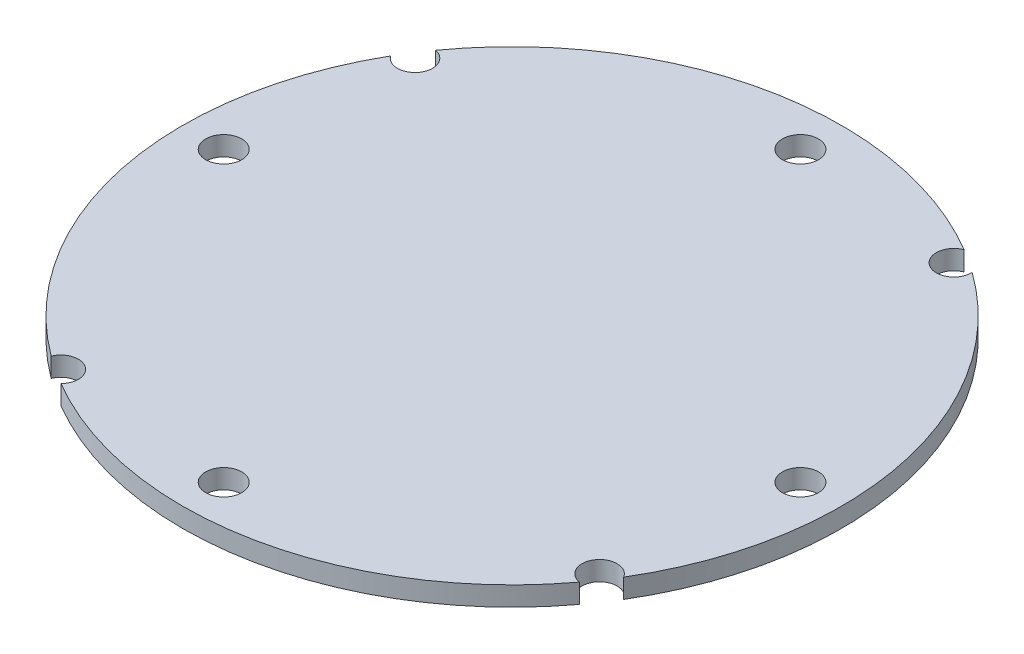
SolidWorks part; units mm, degrees
ref_plane "Front Plane" through (0, 0, 0) normal (0, 0, 1) x (1, 0, 0)
ref_plane "Top Plane" through (0, 0, 0) normal (0, 1, 0) x (1, 0, 0)
ref_plane "Right Plane" through (0, 0, 0) normal (1, 0, 0) x (0, 0, -1)
sketch "Sketch1" plane through (0, 0, 0) normal (0, 1, 0) x (1, 0, 0)
  circle A0 centre (0, 0) radius 63.9
  dimension "PCBdiam" = 127.8
extrude "Boss-Extrude1" add sketch "Sketch1" along normal blind 3.75
hole_wizard "M6 Clearance Hole1" positions "Sketch2" profile "Sketch4" hole size "M6" standard "ANSI Metric" end condition through all
sketch "Sketch2" plane through (0, 3.75, 0) normal (0, 1, 0) x (1, 0, 0)
  line L0 (0, 0) -> (0, 29.5662) construction
  circle A0 centre (0, 0) radius 63.9 construction
  ellipse E2 centre (-116.4291, -176.9435) end of major axis (-117.7556, -176.0714) minor radius 1.3748
  ellipse E3 centre (-116.4291, -176.9435) end of major axis (-117.7556, -176.0714) minor radius 1.3748
  point P7 (-55.9, 0)
  dimension "D1" = 0
  dimension "holeRadius" = 55.9
sketch "Sketch4" plane through (-55.9, 3.75, 0) normal (1, 0, 0) x (0, 0, 1)
  line L0 (0, 0) -> (0, 3.75)
  line L1 (0, 3.75) -> (3.5, 3.75)
  line L2 (3.5, 3.75) -> (3.5, 0)
  line L5 (3.5, 0) -> (0, 0)
  line L11 (0, -6.35) -> (0, 107.95) construction
  dimension "Thru Hole Dia." = 7
  dimension "Thru Hole Depth" = 3.75
pattern_circular "CirPattern1" count 4 over 360 about axis through (0, 3.75, 0) along (0, -1, 0) of "M6 Clearance Hole1"
sketch "Sketch5" plane through (0, 3.75, 0) normal (0, 1, 0) x (1, 0, 0)
  arc A0 (-31.9347, 32.9281) -> (-41.7327, 32.9281) centre (-36.8337, 33.9281) ccw construction
  arc A1 (-31.9347, 32.9281) -> (-41.7327, 32.9281) centre (-36.8337, 33.9281) ccw construction
  circle A2 centre (-36.8337, 33.9281) radius 7
  dimension "D1" = 14
extrude "Cut-Extrude1" [suppressed] cut sketch "Sketch5" against normal through all contours A2
sketch "Sketch6" plane through (0, 0, 0) normal (0, -1, 0) x (1, 0, 0)
  circle A0 centre (33.9101, -51.7223) radius 1.5875 construction
  circle A1 centre (51.7987, 34.8369) radius 1.5875 construction
  circle A2 centre (-34.7605, 52.7256) radius 1.5875 construction
  circle A3 centre (-52.6491, -33.8336) radius 1.5875 construction
  circle A4 centre (33.9101, -51.7223) radius 1.5875
  circle A5 centre (51.7987, 34.8369) radius 1.5875
  circle A6 centre (-34.7605, 52.7256) radius 1.5875
  circle A7 centre (-52.6491, -33.8336) radius 1.5875
  point P13 (-52.6491, -33.8336)
  point P14 (33.9101, -51.7223)
  point P15 (51.7987, 34.8369)
  point P16 (-34.7605, 52.7256)
hole_wizard "Tap Drill for M8x1.25 Tap2" positions "3DSketch1" profile "Sketch9" hole size "M8x1.25" standard "ANSI Metric" end condition through all
sketch3d "3DSketch1"
  point P0 (-34.7605, 0, 52.7256)
  point P3 (51.7987, 0, 34.8369)
  point P6 (33.9101, 0, -51.7223)
  point P9 (-52.6491, 0, -33.8336)
sketch "Sketch9" plane through (-34.7605, 0, 52.7256) normal (1, 0, 0) x (0, 0, -1)
  line L0 (0, 0) -> (0, 3.75)
  line L1 (0, 3.75) -> (3.4, 3.75)
  line L2 (3.4, 3.75) -> (3.4, 0)
  line L5 (3.4, 0) -> (0, 0)
  line L11 (0, -6.35) -> (0, 107.95) construction
  dimension "Thru Hole Dia." = 6.8
  dimension "Thru Hole Depth" = 3.75
